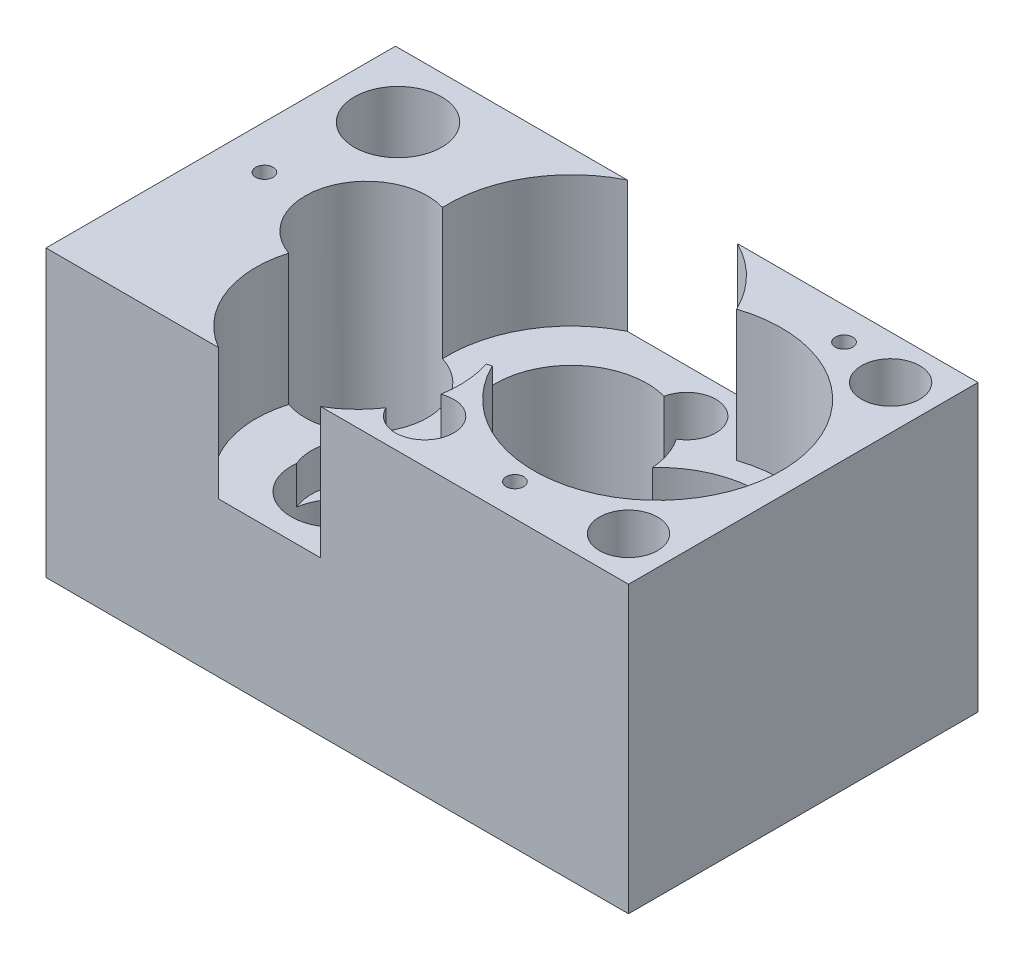
SolidWorks part; units mm, degrees
note: The reader was unsure of these and kept them because the rebuilt part matched: shared geometry of "草图1<4>", "草图1<5>", "草图1<6>", "草图2<3>", "草图2<4>", "草图2<5>".
ref_plane "前视基准面" through (0, 0, 0) normal (0, 0, 1) x (1, 0, 0)
ref_plane "上视基准面" through (0, 0, 0) normal (0, 1, 0) x (1, 0, 0)
ref_plane "右视基准面" through (0, 0, 0) normal (1, 0, 0) x (0, 0, -1)
other "Configuration Table"
sketch "草图1" plane through (0, 0, 0) normal (0, 1, 0) x (1, 0, 0)
  line L1 (0, 0) -> (20, 0)
  line L2 (0, 0) -> (0, -12)
  line L3 (0, -12) -> (20, -12)
  line L4 (20, 0) -> (20, -12)
  circle A0 centre (5, -6) radius 2.1
  circle A4 centre (15, -6) radius 3.5
  circle A6 centre (7.6787, -8.9706) radius 1.6
  circle A7 centre (7.6787, -8.9706) radius 3.5
  circle A8 centre (9.8471, -3.8074) radius 2.6
  circle A9 centre (9.8471, -3.8074) radius 4.25
  circle A10 centre (15, -6) radius 4.25
  dimension "D2" = 4.2
  dimension "D3" = 5.6
  dimension "D6" = 8.5
  dimension "D4" = 20
  dimension "D5" = 7
  dimension "D7" = 7
  dimension "D14" = 3.2
  dimension "D15" = 5.2
  dimension "D17" = 8.5
  dimension "D8" = 4
  dimension "D9" = 5
  dimension "D10" = 6
  dimension "D11" = 12
  dimension "D12" = 5.6
  dimension "D13" = 10
  dimension "D16" = 3.0294
extrude "凸台-拉伸1" add sketch "草图1" along normal blind 5.3
extrude "凸台-拉伸2" add sketch "草图1<4>" along normal blind 1.5 contours A10 A8 A7 | A8 A10 A4 | A7 A8
sketch "草图1<4>" plane through (0, 0, 0) normal (0, 1, 0) x (1, 0, 0) same geometry as "草图1"
extrude "凸台-拉伸3" add sketch "草图1<5>" along normal blind 4 contours A6
sketch "草图1<5>" plane through (0, 0, 0) normal (0, 1, 0) x (1, 0, 0) same geometry as "草图1"
extrude "凸台-拉伸4" add sketch "草图1<6>" along normal blind 4.5 from surface contours A9 L1 L2 L3 A7 A0 | A9 A7 L3 L4 L1 A4
sketch "草图1<6>" plane through (0, 0, 0) normal (0, 1, 0) x (1, 0, 0) same geometry as "草图1"
sketch "草图2" plane through (0, 0, 0) normal (0, 1, 0) x (1, 0, 0)
  line L0 (0, -6) -> (1.5, -6) construction
  line L1 (0, -12) -> (0, 0) construction
  line L2 (20, -12) -> (20, 0) construction
  line L3 (20, 0) -> (11.7355, 0) construction
  line L4 (20, -12) -> (9.4316, -12) construction
  circle A0 centre (2.3, -2.2142) radius 1.5
  circle A1 centre (2.3, -2.2142) radius 0.9
  circle A2 centre (7.7, -9.7858) radius 1.5
  circle A3 centre (7.7, -9.7858) radius 0.9
  circle A4 centre (11.5, -1.5) radius 0.7
  circle A5 centre (11.5, -1.5) radius 1
  circle A6 centre (18.5, -10.5) radius 0.7
  circle A7 centre (18.5, -10.5) radius 1
  circle A8 centre (18.5, -1.5) radius 1
  circle A9 centre (18.5, -1.5) radius 0.7
  circle A10 centre (11.5, -10.5) radius 1
  circle A11 centre (11.5, -10.5) radius 0.7
  circle A20 centre (1.5, -6) radius 0.3
  circle A21 centre (16.5, -1.1) radius 0.3
  circle A22 centre (15, -10.9) radius 0.3
  dimension "D1" = 1.8
  dimension "D2" = 3
  dimension "D3" = 1.4
  dimension "D4" = 2
  dimension "D5" = 0.6
  dimension "D6" = 1.5
  dimension "D7" = 3.5
  dimension "D8" = 1.1
  dimension "D9" = 1.1
  dimension "D10" = 5
extrude "切除-拉伸1" cut sketch "草图2" along normal through all contours A1 | A3 | A11 | A6 | A9 | A4
extrude "切除-拉伸2" cut sketch "草图2<3>" against normal offset from surface (8.8 mm away) 1 from surface at 9.8 contours A0 | A2 up to face at (2.3, 0, 3.1142) starting at face at (2.3, 9.8, 3.1142)
sketch "草图2<3>" plane through (0, 0, 0) normal (0, 1, 0) x (1, 0, 0) same geometry as "草图2"
extrude "切除-拉伸3" cut sketch "草图2<4>" against normal offset from surface (7.8 mm away) 2 from surface at 9.8 contours A5 | A8 | A7 | A10 up to face at (2.3, 0, 3.1142) starting at face at (2.3, 9.8, 3.7142)
sketch "草图2<4>" plane through (0, 0, 0) normal (0, 1, 0) x (1, 0, 0) same geometry as "草图2"
extrude "切除-拉伸4" cut sketch "草图2<5>" against normal blind 6 from surface at 9.8 contours A20 | A21 | A22 starting at face at (2.3, 9.8, 3.7142)
sketch "草图2<5>" plane through (0, 0, 0) normal (0, 1, 0) x (1, 0, 0) same geometry as "草图2"
